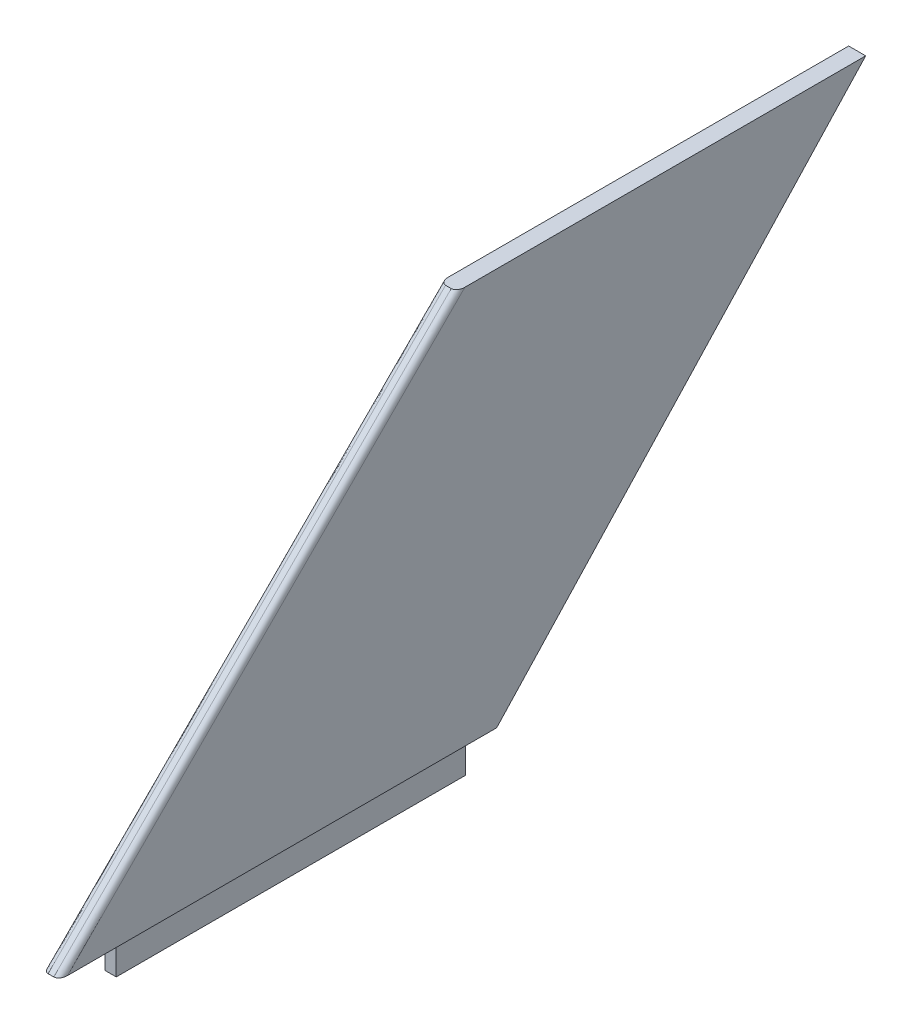
SolidWorks part; units mm, degrees
ref_plane "Спереди" through (0, 0, 0) normal (0, 0, 1) x (1, 0, 0)
ref_plane "Сверху" through (0, 0, 0) normal (0, 1, 0) x (1, 0, 0)
ref_plane "Справа" through (0, 0, 0) normal (1, 0, 0) x (0, 0, -1)
other "Configuration Table"
sketch "Эскиз1" plane through (0, 0, 0) normal (1, 0, 0) x (0, 0, -1)
  line L0 (0, 0) -> (77, 0)
  line L1 (77, 0) -> (142, 70)
  line L2 (142, 70) -> (70, 70)
  line L3 (70, 70) -> (0, 0)
  line L4 (72, 0) -> (72, -5)
  line L5 (72, -5) -> (10.5, -5)
  line L6 (10.5, -5) -> (10.5, 0)
  line L7 (142, 70) -> (142, 0) construction
  line L8 (142, 0) -> (77, 0) construction
  dimension "D1" = 5
  dimension "D2" = 5
  dimension "D3" = 77
  dimension "D4" = 61.5
  dimension "D5" = 72
  dimension "D6" = 70
  dimension "D7" = 65
extrude "Бобышка-Вытянуть1" add sketch "Эскиз1" along normal blind 1.5 and the other way blind 1.5 contours L2 L3 L0 L1 region at (0, 34.6085, -71.8725)
extrude "Бобышка-Вытянуть2" add sketch "Эскиз1<3>" along normal blind 1 and the other way blind 1 contours L6 L5 L4 L0 region at (0, -2.5, -41.25)
sketch "Эскиз1<3>" plane through (0, 0, 0) normal (1, 0, 0) x (0, 0, -1) same geometry as "Эскиз1"
fillet "Скругление1" radius 1 2 edges at (-1.5, 35, -35) (1.5, 35, -35) first distance on face at (0, 35, -35)
